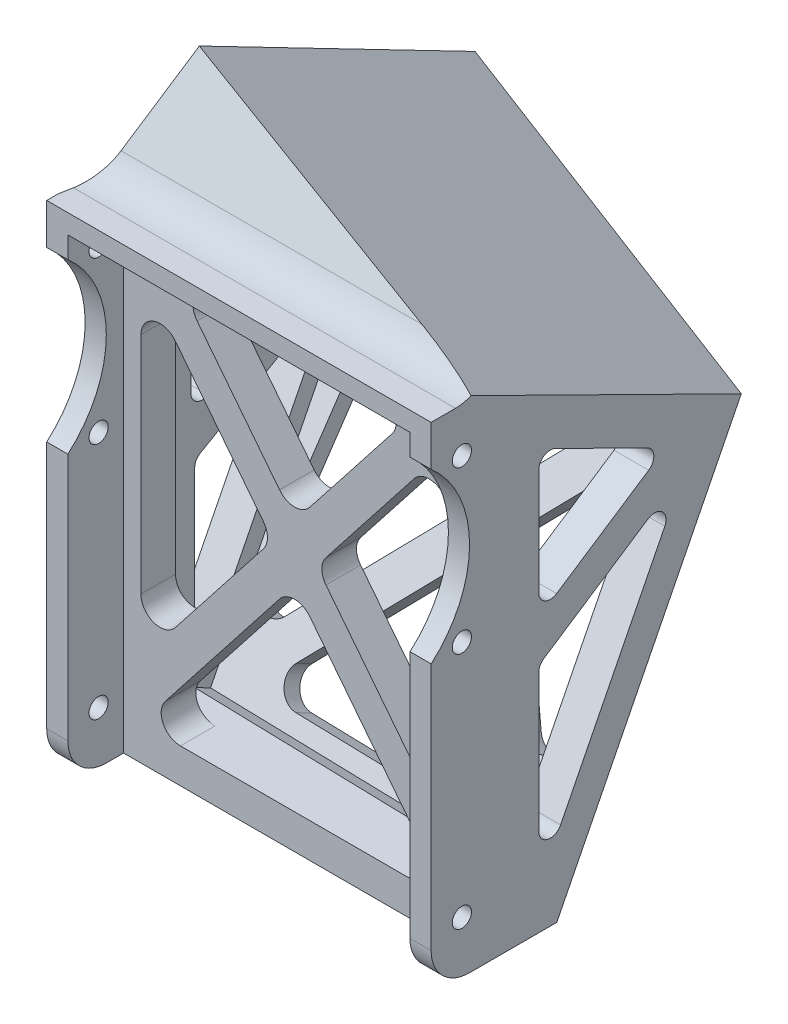
SolidWorks part; units mm, degrees
ref_plane "Front Plane" through (0, 0, 0) normal (0, 0, 1) x (1, 0, 0)
ref_plane "Top Plane" through (0, 0, 0) normal (0, 1, 0) x (1, 0, 0)
ref_plane "Right Plane" through (0, 0, 0) normal (1, 0, 0) x (0, 0, -1)
sketch "Sketch1" plane through (0, 0, 0) normal (0, 0, 1) x (1, 0, 0)
  line L1 (-25, 37.5) -> (25, 37.5)
  line L2 (-25, 37.5) -> (-25, -37.5)
  line L3 (-25, -37.5) -> (25, -37.5)
  line L4 (25, 37.5) -> (25, -37.5)
  line L5 (-25, 37.5) -> (25, -37.5) construction
  line L6 (-25, -37.5) -> (25, 37.5) construction
  point P0 (0, 0)
  dimension "D1" = 50
  dimension "D2" = 75
extrude "Boss-Extrude1" add sketch "Sketch1" along normal mid plane 50
sketch "Sketch3" plane through (0, 0, 25) normal (0, 0, 1) x (1, 0, 0)
  line L0 (-25, -37.5) -> (25, -37.5) construction
  line L1 (-22.25, 12.5) -> (22.25, 12.5)
  line L2 (-22.25, 12.5) -> (-22.25, -37.5)
  line L3 (-22.25, -37.5) -> (22.25, -37.5)
  line L4 (22.25, 12.5) -> (22.25, -37.5)
  line L5 (-22.25, 12.5) -> (22.25, -37.5) construction
  line L6 (-22.25, -37.5) -> (22.25, 12.5) construction
  point P0 (0, -12.5)
  dimension "D1" = 44.5
  dimension "D2" = 50
extrude "Cut-Extrude2" cut sketch "Sketch3" against normal blind 5.6
ref_plane "Plane1" through (18.7846, -15.6227, 40.673) normal (0.9392, -0.2961, 0.1736) x (0.023, -0.4504, -0.8925)
sketch "Sketch2" plane through (18.7846, -15.6227, 40.673) normal (0.9392, -0.2961, 0.1736) x (0.023, -0.4504, -0.8925)
  line L0 (-10.9444, 36.2708) -> (42.5099, 36.2708)
  line L3 (-10.9444, 74.2068) -> (-10.9444, 36.2708)
  line L4 (33.6826, 57.0807) -> (34.8331, 74.2068)
  line L5 (-10.9444, 36.2708) -> (33.6826, 57.0807)
  line L6 (-9.7938, 53.3969) -> (-10.9444, 36.2708)
  line L7 (34.8331, 74.2068) -> (-9.7938, 53.3969)
  line L8 (33.6826, 57.0807) -> (34.8331, 74.2068) construction
  line L9 (-10.9444, 36.2708) -> (33.6826, 57.0807) construction
  line L10 (-9.7938, 53.3969) -> (-10.9444, 36.2708) construction
  line L11 (34.8331, 74.2068) -> (-9.7938, 53.3969) construction
  line L13 (68.6118, -26.9012) -> (68.6118, 74.2068)
  line L14 (68.6118, 74.2068) -> (-10.9444, 74.2068)
  line L15 (42.5099, 36.2708) -> (42.5099, -26.9012)
  line L22 (42.5099, -26.9012) -> (68.6118, -26.9012)
  point P15 (-5.9901, 11.2025)
  dimension "D2" = 48.5
  dimension "D1" = 0
extrude "Cut-Extrude1" cut sketch "Sketch2" against normal through all both and the other way through all
sketch "Sketch5" plane through (4.3219, 10.6281, -5.2516) normal (0.3425, 0.8423, -0.4162) x (0.9395, -0.3071, 0.1517)
  line L0 (-23.2098, 14.2489) -> (-24.4872, -37.8876)
  line L1 (-31.2098, 14.4449) -> (22.0094, 13.141) construction
  line L2 (-31.2098, -39.0254) -> (22.0094, -30.0181) construction
  line L3 (-31.2098, -39.0254) -> (-31.2098, 14.4449) construction
  line L4 (-31.2098, 14.4449) -> (-23.2098, 14.2489)
  line L5 (-31.2098, 14.4449) -> (-31.2098, -39.0254)
  line L6 (-31.2098, -39.0254) -> (-24.4872, -37.8876)
  dimension "D1" = 8
extrude "Cut-Extrude4" cut sketch "Sketch5" against normal through all
sketch "Sketch6" plane through (-22.1206, 6.9746, -4.0897) normal (-0.9392, 0.2961, -0.1736) x (-0.1656, 0.0522, 0.9848)
  line L0 (29.5385, 6.6925) -> (21.4935, 23.945)
  line L1 (29.5385, 27.6964) -> (-17.7274, 5.656) construction
  line L3 (21.4935, 23.945) -> (29.5385, 27.6964)
  line L4 (29.5385, 27.6964) -> (29.5385, 6.6925)
  line L5 (-8.4538, -14.2314) -> (-17.7274, 5.656) construction
  point P5 (7.3907, 17.3688)
extrude "Cut-Extrude5" cut sketch "Sketch6" against normal through all
sketch "Sketch37" plane through (-25, 0, 0) normal (-1, 0, 0) x (0, 0, 1)
  line L0 (2.9555, -37.5) -> (9.0108, -49.5)
  line L1 (9.0108, -49.5) -> (25, -49.5)
  line L2 (25, -49.5) -> (25, -37.5)
  line L3 (-12.4151, -7.0396) -> (2.9555, -37.5) construction
  line L4 (25, -37.5) -> (2.9555, -37.5) construction
  line L5 (2.9555, -37.5) -> (25, -37.5)
  dimension "D1" = 12
extrude "Boss-Extrude9" add sketch "Sketch37" against normal up to surface (50 mm away) up to face at (25, -14.9462, 10.1378)
sketch "Sketch38" plane through (0, 0, 25) normal (0, 0, 1) x (1, 0, 0)
  line L0 (-22.25, -37.5) -> (-22.25, -49.5)
  line L1 (25, -49.5) -> (-25, -49.5) construction
  line L2 (-22.25, -49.5) -> (22.25, -49.5)
  line L3 (22.25, -49.5) -> (22.25, -37.5)
  line L4 (22.25, -37.5) -> (-22.25, -37.5)
  line L5 (22.25, -37.5) -> (22.25, 12.5) construction
extrude "Cut-Extrude27" cut sketch "Sketch38" against normal up to surface (5.6 mm away) up to face at (0, -12.5, 19.4)
sketch "Sketch39" plane through (0.3147, -6.1595, -12.2065) normal (0.023, -0.4504, -0.8925) x (-0.9997, -0.0104, -0.0205)
  line L1 (-31.1983, -28.5366) -> (58.2293, -28.5366)
  line L2 (-31.1983, -28.5366) -> (-31.1983, -65.0499)
  line L3 (-31.1983, -65.0499) -> (58.2293, -65.0499)
  line L4 (58.2293, -28.5366) -> (58.2293, -65.0499)
extrude "Cut-Extrude28" cut sketch "Sketch39" along normal through all
shell "Shell1" thickness 4.5
sketch "Sketch14" plane through (0, 17, 0) normal (0, 1, 0) x (1, 0, 0)
  line L4 (5.8251, -19.6931) -> (0.001, -14.9)
  line L5 (0.001, -14.9) -> (-17.6793, -14.9)
  line L6 (-17.6793, -14.9) -> (-18.4498, -19.0673)
  line L7 (-18.4498, -19.0673) -> (5.8251, -19.6931)
  line L8 (5.8251, -19.6931) -> (0.001, -14.9)
  line L9 (0.001, -14.9) -> (-17.6793, -14.9)
  line L10 (-17.6793, -14.9) -> (-18.4498, -19.0673)
  line L13 (-18.4498, -19.0673) -> (5.8251, -19.6931)
  dimension "D1" = 0
extrude "Boss-Extrude5" add sketch "Sketch14" along normal up to next
sketch "Sketch19" plane through (0, 0, 19.4) normal (0, 0, 1) x (1, 0, 0)
  line L3 (22.25, -49.5) -> (-22.25, -49.5) construction
  line L7 (-22.25, 12.5) -> (-22.25, -49.5) construction
  line L11 (22.25, -49.5) -> (22.25, 12.5) construction
  line L15 (-22.25, 12.5) -> (22.25, -44.2227) construction
  line L19 (22.25, -49.5) -> (22.25, 12.5) construction
  line L20 (22.25, 12.5) -> (-22.25, 12.5) construction
  line L24 (22.25, 12.5) -> (-22.25, -44.2227) construction
  line L25 (-22.25, 12.5) -> (-22.25, -49.5) construction
  line L28 (-15.8599, 8) -> (0, -12.2161)
  line L30 (0, -12.2161) -> (15.8599, 8)
  line L31 (15.8599, 8) -> (-15.8599, 8)
  line L33 (-20, 5.9867) -> (-2.8598, -15.8614)
  line L34 (-2.8598, -15.8614) -> (-20, -37.7095)
  line L35 (-20, -37.7095) -> (-20, 5.9867)
  line L36 (0, -19.5066) -> (-20, -45)
  line L37 (-20, -45) -> (20, -45)
  line L38 (20, -45) -> (0, -19.5066)
  line L39 (2.8598, -15.8614) -> (20, -37.7095)
  line L40 (20, -37.7095) -> (20, 5.9867)
  line L41 (20, 5.9867) -> (2.8598, -15.8614)
  dimension "D1" = 2.25
  dimension "D3" = 2.25
  dimension "D5" = 2.25
  dimension "D7" = 2.25
  dimension "D9" = 4.5
  dimension "D2" = 2.25
  dimension "D4" = 2.25
  dimension "D6" = 4.5
  dimension "D8" = 2.25
  dimension "D10" = 4.5
extrude "Cut-Extrude12" cut sketch "Sketch19" against normal blind 4.5
sketch "Sketch23" plane through (0.3147, -6.1595, -12.2065) normal (0.023, -0.4504, -0.8925) x (-0.9997, -0.0104, -0.0205)
  line L5 (-20.2942, -46.0111) -> (20.7166, -45.5349)
  line L7 (-20.2942, -46.0111) -> (20.7166, -45.5349)
  line L13 (20.7166, -45.5349) -> (20.7166, -1.1994)
  line L19 (-20.2942, 1.24) -> (-20.2942, -46.0111)
  line L22 (15.1175, 14.1541) -> (-20.2942, 1.24)
  line L23 (20.7166, -1.1994) -> (15.1175, 14.1541)
  line L26 (20.7166, -45.5349) -> (20.7166, -1.1994)
  line L32 (-20.2942, 1.24) -> (-20.2942, -46.0111)
  line L35 (15.1175, 14.1541) -> (-20.2942, 1.24)
  line L36 (20.7166, -1.1994) -> (15.1175, 14.1541)
  dimension "D1" = 0
extrude "Cut-Extrude14" cut sketch "Sketch23" against normal up to next from offset 2.25 offset against normal yes
sketch "Sketch25" plane through (0.3147, -6.1595, -12.2065) normal (0.023, -0.4504, -0.8925) x (-0.9997, -0.0104, -0.0205)
  line L0 (-20.2942, 1.24) -> (20.7166, -45.5349) construction
  line L1 (-20.2942, -46.0111) -> (15.1175, 14.1541) construction
  line L2 (15.1175, 14.1541) -> (20.7166, -45.5349) construction
  line L3 (-20.2942, -2.1729) -> (-6.418, -17.9994)
  line L4 (-6.418, -17.9994) -> (-20.2942, -41.5753)
  line L5 (20.7166, -1.1994) -> (15.1175, 14.1541)
  line L6 (20.7166, -45.5349) -> (20.7166, -1.1994)
  line L7 (-20.2942, -46.0111) -> (20.7166, -45.5349)
  line L8 (-20.2942, 1.24) -> (-20.2942, -46.0111)
  line L9 (15.1175, 14.1541) -> (-20.2942, 1.24)
  line L10 (20.7166, -1.1994) -> (15.1175, 14.1541) construction
  line L11 (20.7166, -45.5349) -> (20.7166, -1.1994) construction
  line L13 (-20.2942, 1.24) -> (-20.2942, -46.0111) construction
  line L14 (15.1175, 14.1541) -> (-20.2942, 1.24) construction
  line L15 (-20.2942, -41.5753) -> (-20.2942, -2.1729)
  line L16 (-18.0268, 2.0669) -> (-4.0142, -13.9152)
  line L17 (-4.0142, -13.9152) -> (11.7931, 12.9417)
  line L18 (11.7931, 12.9417) -> (-18.0268, 2.0669)
  line L19 (15.4764, 10.3281) -> (-0.8899, -17.4786)
  line L20 (-0.8899, -17.4786) -> (20.3581, -41.7131)
  line L21 (20.3581, -41.7131) -> (15.4764, 10.3281)
  line L22 (-16.332, -43.715) -> (-3.2938, -21.5628)
  line L23 (-3.2938, -21.5628) -> (15.8015, -43.3418)
  line L24 (15.8015, -43.3418) -> (-16.332, -43.715)
  line L30 (-20.2942, -46.0111) -> (20.7166, -45.5349)
  dimension "D3" = 2.25
  dimension "D5" = 2.25
  dimension "D2" = 4.5
  dimension "D4" = 4.5
  dimension "D6" = 2.25
extrude "Cut-Extrude18" cut sketch "Sketch25" against normal up to next contours L24 L23 L22 | L20 L21 L19 | L17 L18 L16 | L15 L4 L3 region at (15.9794, -24.3727, -2.6121) region at (3.7298, -5.7987, -12.3005) region at (-11.3304, -20.8217, -5.1081) region at (1.5891, -38.4706, 4.1308)
sketch "Sketch26" plane through (25, 0, 0) normal (1, 0, 0) x (0, 0, -1)
  line L0 (-14.9, -45) -> (-12.9549, -45) construction
  line L7 (-25, -49.5) -> (-10.2999, -49.5) construction
  line L8 (8.3318, -2.8154) -> (-14.9, -18.168) construction
  line L9 (3.8238, -3.0976) -> (-12.65, -13.9842)
  line L10 (-14.9, -45) -> (-12.9549, -45)
  line L11 (-14.9, 8.664) -> (-14.9, -45)
  line L12 (8.3318, -2.8154) -> (-14.9, 8.664)
  line L13 (-12.9549, -45) -> (8.3318, -2.8154)
  line L14 (3.8238, -3.0976) -> (-12.65, 5.0425)
  line L19 (-14.9, 8.664) -> (-14.9, -45) construction
  line L20 (8.3318, -2.8154) -> (-14.9, 8.664) construction
  line L21 (-12.9549, -45) -> (8.3318, -2.8154) construction
  line L22 (3.8238, -3.0976) -> (-15.8967, 6.6468) construction
  line L23 (3.8238, -3.0976) -> (-16.1405, -16.2909) construction
  line L24 (-12.65, 5.0425) -> (-12.65, -13.9842)
  line L25 (-12.65, -19.378) -> (6.29, -6.8616)
  line L26 (6.29, -6.8616) -> (-12.65, -44.3957)
  line L27 (-12.65, -44.3957) -> (-12.65, -19.378)
  point P16 (-12.65, -20.2652)
  dimension "D3" = 2.25
  dimension "D2" = 2.25
  dimension "D4" = 2.25
extrude "Cut-Extrude19" cut sketch "Sketch26" against normal up to next contours L14 L24 L9 | L27 L26 L25 | L24 L9 L14 | L27 L25 L26 region at (25, -4.0131, 7.1587) region at (25, -23.5451, 6.3367)
sketch "Sketch27" plane through (-25, 0, 0) normal (-1, 0, 0) x (0, 0, 1)
  line L0 (-8.0754, -5.4183) -> (14.9, -18.4731) construction
  line L8 (14.9, -18.4731) -> (14.9, -45) construction
  line L9 (14.9, -18.4731) -> (14.9, 8.0539) construction
  line L10 (-6.2446, -9.0464) -> (11.8979, -45)
  line L11 (14.9, -45) -> (14.9, 8.0539)
  line L12 (11.8979, -45) -> (14.9, -45)
  line L13 (-8.0754, -5.4183) -> (11.8979, -45)
  line L14 (14.9, 8.0539) -> (-8.0754, -5.4183)
  line L24 (11.8979, -45) -> (14.9, -45) construction
  line L27 (-8.0754, -5.4183) -> (11.8979, -45) construction
  line L28 (14.9, 8.0539) -> (-8.0754, -5.4183) construction
  line L29 (11.8979, -45) -> (11.8979, -19.3551)
  line L30 (11.8979, -19.3551) -> (-6.2446, -9.0464)
  line L31 (-3.0749, -5.3843) -> (12.4, -14.1772)
  line L32 (12.4, -14.1772) -> (12.4, 3.6898)
  line L33 (12.4, 3.6898) -> (-3.0749, -5.3843)
  point P11 (0, 0)
  dimension "D2" = 2.25
  dimension "D3" = 2.5
extrude "Cut-Extrude20" cut sketch "Sketch27" against normal up to next contours L29 L30 L10 | L32 L33 L31 region at (-25, -24.4672, 5.8504) region at (-25, -5.2905, 7.2417)
sketch "Sketch28" plane through (-22.1206, 6.9746, -4.0897) normal (-0.9392, 0.2961, -0.1736) x (-0.1656, 0.0522, 0.9848)
  line L0 (-6.8798, -12.2829) -> (18.4892, 17.5789) construction
  line L1 (2.4946, -4.7236) -> (18.4892, 4.0853)
  line L2 (18.4892, 4.0853) -> (18.4892, 14.1037)
  line L3 (18.4892, 14.1037) -> (2.4946, -4.7236)
  line L4 (-8.3663, -3.7711) -> (-11.7472, 3.4794)
  line L5 (-11.7472, 3.4794) -> (13.6, 15.299)
  line L6 (-8.3663, -3.7711) -> (1.1815, 0.6811)
  line L7 (18.4892, 1.5166) -> (18.4892, 17.5789)
  line L8 (-4.8406, -11.332) -> (18.4892, 1.5166)
  line L9 (-4.8406, -11.332) -> (18.4892, 1.5166)
  line L10 (-13.7864, 2.5285) -> (-6.8798, -12.2829)
  line L11 (18.4892, 17.5789) -> (-13.7864, 2.5285)
  line L13 (18.4892, 1.5166) -> (18.4892, 17.5789) construction
  line L16 (-13.7864, 2.5285) -> (-6.8798, -12.2829) construction
  line L17 (18.4892, 17.5789) -> (-13.7864, 2.5285) construction
  line L18 (13.6, 15.299) -> (1.1815, 0.6811)
  line L24 (-6.8798, -12.2829) -> (-4.8406, -11.332)
  line L25 (-6.8798, -12.2829) -> (-4.8406, -11.332)
  point P1 (-2.8558, -4.0712)
  point P5 (18.4892, 4.2753)
  point P8 (1.2886, 0.8073)
  point P12 (0.6134, -6.9379)
  dimension "D3" = 2.25
  dimension "D5" = 2.25
  dimension "D2" = 2.25
  dimension "D4" = 4.5
  dimension "D6" = 8
extrude "Cut-Extrude21" cut sketch "Sketch28" against normal up to surface (4.5 mm away) contours L18 L5 L4 | L2 L3 L1 region at (-22.9499, 11.9424, 8.868) region at (-20.5288, 11.4503, -5.0667)
sketch "Sketch29" plane through (4.3219, 10.6281, -5.2516) normal (0.3425, 0.8423, -0.4162) x (0.9395, -0.3071, 0.1517)
  line L5 (-24.1693, -24.9136) -> (-24.3342, -31.6429)
  line L6 (-24.2698, -29.0136) -> (-23.2098, 14.2489) construction
  line L7 (-24.1693, -24.9136) -> (25.1433, -24.9136)
  line L9 (25.1433, -24.9136) -> (24.9488, -32.8504)
  line L10 (-24.3342, -31.6429) -> (24.9488, -32.8504)
  line L11 (21.3419, -30.1311) -> (-24.2698, -29.0136) construction
  point P8 (-24.3468, -25.0539)
  point P10 (0, 0)
  point P11 (0, 0)
  point P13 (25.1433, -32.8504)
  dimension "D1" = 4.1
extrude "Cut-Extrude22" cut sketch "Sketch29" against normal offset from surface (16.724 mm away) 2.5 up to face at (0, 12.5, 22.2)
sketch "Sketch31" plane through (0, 0, 25) normal (0, 0, 1) x (1, 0, 0)
  line L3 (25, -49.5) -> (25, 15)
  line L4 (25, -49.5) -> (25, 15)
  line L5 (25, 15) -> (-23.038, 15)
  line L6 (25, 15) -> (-25, 15)
  line L16 (-25, 14.8998) -> (-25, -49.5)
  line L29 (-23.038, 15) -> (-25, 14.8998)
  line L30 (-25, 15) -> (-25, -49.5)
  line L32 (-22.25, -49.5) -> (-22.25, 12.5)
  line L33 (-22.25, -49.5) -> (-22.25, 12.5)
  line L34 (-22.25, 12.5) -> (22.25, 12.5)
  line L35 (-22.25, 12.5) -> (22.25, 12.5)
  line L36 (22.25, 12.5) -> (22.25, -49.5)
  line L37 (22.25, 12.5) -> (22.25, -49.5)
  line L38 (-25, -49.5) -> (-22.25, -49.5)
  line L39 (-25, -49.5) -> (-22.25, -49.5)
  line L40 (22.25, -49.5) -> (25, -49.5)
  line L41 (22.25, -49.5) -> (25, -49.5)
  point P2 (-25, 15.0358)
  point P3 (-24.9796, 14.9499)
  point P5 (-25.0127, 15.0755)
  point P6 (-24.8126, 15)
  dimension "D1" = 0
extrude "Boss-Extrude6" add sketch "Sketch31" along normal blind 1.65 and the other way blind 0.1
sketch "Sketch30" plane through (-25, 0, 0) normal (-1, 0, 0) x (0, 0, 1)
  line L0 (36.15, -1.25) -> (26.65, -1.25) construction
  line L2 (24.9, 15) -> (20.3773, 15) construction
  line L3 (26.65, 9.7045) -> (26.65, -12.2045)
  line L4 (26.65, 15) -> (26.65, -49.5) construction
  circle A0 centre (36.15, -1.25) radius 13 construction
  arc A1 (26.65, 9.7045) -> (26.65, -12.2045) centre (36.15, -1.25) ccw
  point P4 (26.65, -1.25)
  dimension "D1" = 16.25
  dimension "D3" = 26
  dimension "D4" = 1.5
  dimension "D2" = 9.5
extrude "Cut-Extrude23" cut sketch "Sketch30" against normal through all
sketch "Sketch32" plane through (-22.1206, 6.9746, -4.0897) normal (-0.9392, 0.2961, -0.1736) x (-0.1656, 0.0522, 0.9848)
  line L1 (28.0651, 7.7221) -> (32.0751, 7.7221)
  line L2 (28.0651, 7.7221) -> (28.0651, 5.2637)
  line L3 (28.0651, 5.2637) -> (32.0751, 5.2637)
  line L4 (32.0751, 7.7221) -> (32.0751, 5.2637)
extrude "Cut-Extrude24" cut sketch "Sketch32" along normal through all
sketch "Sketch34" plane through (-25, 0, 0) normal (-1, 0, 0) x (0, 0, 1)
  line L0 (22.65, 9.25) -> (22.65, -11.75) construction
  line L2 (26.65, 15) -> (26.65, 9.7045) construction
  line L3 (22.65, 9.25) -> (26.65, 9.25) construction
  line L4 (25.171, 15) -> (20.3773, 15) construction
  line L5 (22.65, -11.75) -> (22.65, -42.75) construction
  circle A0 centre (22.65, 9.25) radius 1.25
  circle A1 centre (22.65, -11.75) radius 1.25
  circle A2 centre (22.65, -42.75) radius 1.25
  dimension "D1" = 2.5
  dimension "D2" = 4
  dimension "D3" = 5.75
  dimension "D4" = 21
  dimension "D5" = 52
extrude "Cut-Extrude25" cut sketch "Sketch34" against normal through all
fillet "Fillet2" radius 2.5 12 edges at (20, 5.9867, 17.15) (0, -19.5066, 17.15) (0, -12.2161, 17.15) (-2.8598, -15.8614, 17.15) (-20, 5.9867, 17.15) (-20, -37.7095, 17.15) (20, -37.7095, 17.15) (20, -45, 17.15) (-20, -45, 17.15) (2.8598, -15.8614, 17.15) (-15.8599, 8, 17.15) (15.8599, 8, 17.15)
fillet "Fillet3" radius 2.5 7 edges at (-18.8283, 20.7247, 14.5093) (-21.8409, 1.9335, -1.2424) (-17.0156, 9.0132, -15.2678) (-17.6591, 21.6094, 9.6944) (-21.8409, 11.17, 14.5093) (-19.9982, 7.0196, -2.5355) (-19.7557, 2.2749, -11.9382)
fillet "Fillet5" radius 2.5 12 edges at (20.5777, -42.5599, 7.9443) (4.302, -18.0344, -4.8511) (6.7052, -21.6557, -2.9618) (1.1785, -21.2481, -3.31) (-15.5085, -44.5112, 7.9986) (16.6165, -44.5112, 8.8268) (3.5817, -24.8694, -1.4207) (-11.5012, 5.779, -17.275) (-15.1834, 3.4074, -16.1732) (-20.0639, -43.1043, 7.1712) (20.5777, -7.3824, -9.8066) (18.3109, -3.6207, -11.7632)
fillet "Fillet6" radius 5 1 edges at (0.2994, 15, 20.3773)
fillet "Fillet7" radius 1.5 6 edges at (22.75, -44.3957, 12.65) (22.75, -6.8616, -6.29) (22.75, -19.378, 12.65) (22.75, -13.9842, 12.65) (22.75, 5.0425, 12.65) (22.75, -3.0976, -3.8238)
fillet "Fillet8" radius 1.5 6 edges at (-22.75, -14.1772, 12.4) (-22.75, -5.3843, -3.0749) (-22.75, 3.6898, 12.4) (-22.75, -45, 11.8979) (-22.75, -19.3551, 11.8979) (-22.75, -9.0464, -6.2446)
fillet "Fillet9" radius 5 2 edges at (23.625, -49.5, 26.65) (-23.625, -49.5, 26.65)
equation "\"t\"= 4.5mm"
equation "\"D1@Shell1\"=\"t\""
equation "\"D1@Sketch19\"=\"t\"/2"
equation "\"D7@Sketch19\"=\"t\"/2"
equation "\"D3@Sketch19\"=\"t\"/2"
equation "\"D5@Sketch19\"=\"t\"/2"
equation "\"D1@Cut-Extrude12\"=\"t\""
equation "\"D19@Cut-Extrude14\"=\"t\"/2"
equation "\"D2@Sketch25\"=\"t\""
equation "\"D3@Sketch25\"=\"t\"/2"
equation "\"D4@Sketch25\"=\"t\""
equation "\"D5@Sketch25\"=\"t\"/2"
equation "\"D3@Sketch28\"=\"t\"/2"
equation "\"D4@Sketch28\"=\"t\""
equation "\"D5@Sketch28\"=\"t\"/2"
equation "\"D9@Sketch19\"=\"t\""
equation "\"D2@Sketch19\"=\"t\"/2"
equation "\"D4@Sketch19\"=\"t\"/2"
equation "\"D6@Sketch19\"=\"t\""
equation "\"D8@Sketch19\"=\"t\"/2"
equation "\"D10@Sketch19\"=\"t\""
equation "\"D6@Sketch25\"=\"t\"/2"
equation "\"D2@Sketch26\"=\"t\"/2"
equation "\"D3@Sketch26\"=\"t\"/2"
equation "\"D4@Sketch26\"=\"t\"/2"
equation "\"D2@Sketch27\"=\"t\"/2"
equation "\"D2@Sketch28\"=\"t\"/2"
